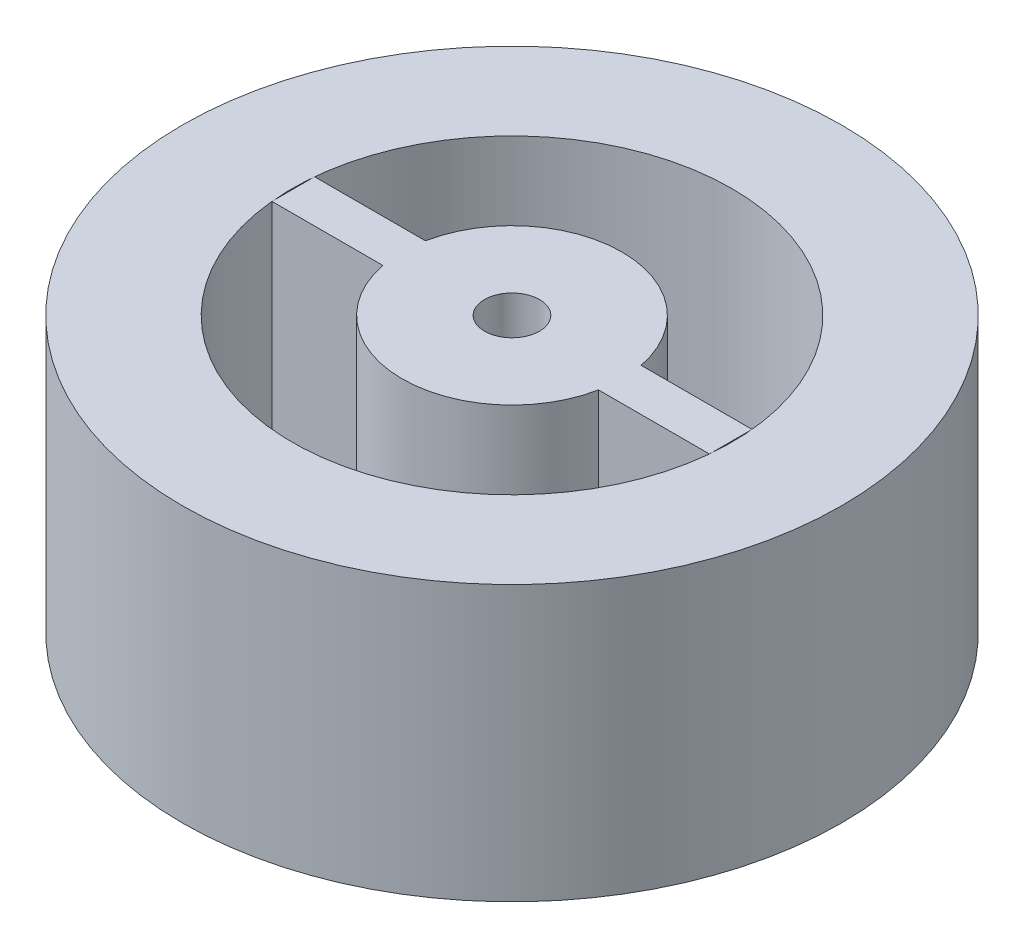
SolidWorks part; units mm, degrees
ref_plane "Front Plane" through (0, 0, 0) normal (0, 0, 1) x (1, 0, 0)
ref_plane "Top Plane" through (0, 0, 0) normal (0, 1, 0) x (1, 0, 0)
ref_plane "Right Plane" through (0, 0, 0) normal (1, 0, 0) x (0, 0, -1)
sketch "Sketch2" plane through (0, 0, 0) normal (0, 1, 0) x (1, 0, 0)
  circle A0 centre (0, 0) radius 6
  circle A1 centre (0, 0) radius 0.5
  dimension "D1" = 12
  dimension "D2" = 1
extrude "Boss-Extrude1" add sketch "Sketch2" along normal blind 5
sketch "Sketch4" plane through (0, 0, 0) normal (0, -1, 0) x (1, 0, 0)
  circle A0 centre (0, 0) radius 4
  circle A1 centre (0, 0) radius 2
  dimension "D1" = 8
  dimension "D2" = 4
extrude "Cut-Extrude1" cut sketch "Sketch4" against normal through all both and the other way through all
sketch "Sketch5" plane through (0, 0, 0) normal (0, -1, 0) x (1, 0, 0)
  line L1 (-3.9812, -0.3878) -> (3.9812, -0.3878)
  line L2 (-3.9812, -0.3878) -> (-3.9812, 0.3878)
  line L3 (-3.9812, 0.3878) -> (3.9812, 0.3878)
  line L4 (3.9812, -0.3878) -> (3.9812, 0.3878)
  line L5 (-3.9812, -0.3878) -> (3.9812, 0.3878) construction
  line L6 (-3.9812, 0.3878) -> (3.9812, -0.3878) construction
  circle A0 centre (0, 0) radius 4 construction
  point P0 (0, 0)
extrude "Boss-Extrude2" add sketch "Sketch5" against normal blind 5
sketch "Sketch6" plane through (0, 0, 0) normal (0, -1, 0) x (1, 0, 0)
  circle A0 centre (0, 0) radius 0.5
extrude "Cut-Extrude2" cut sketch "Sketch6" against normal through all both and the other way through all
